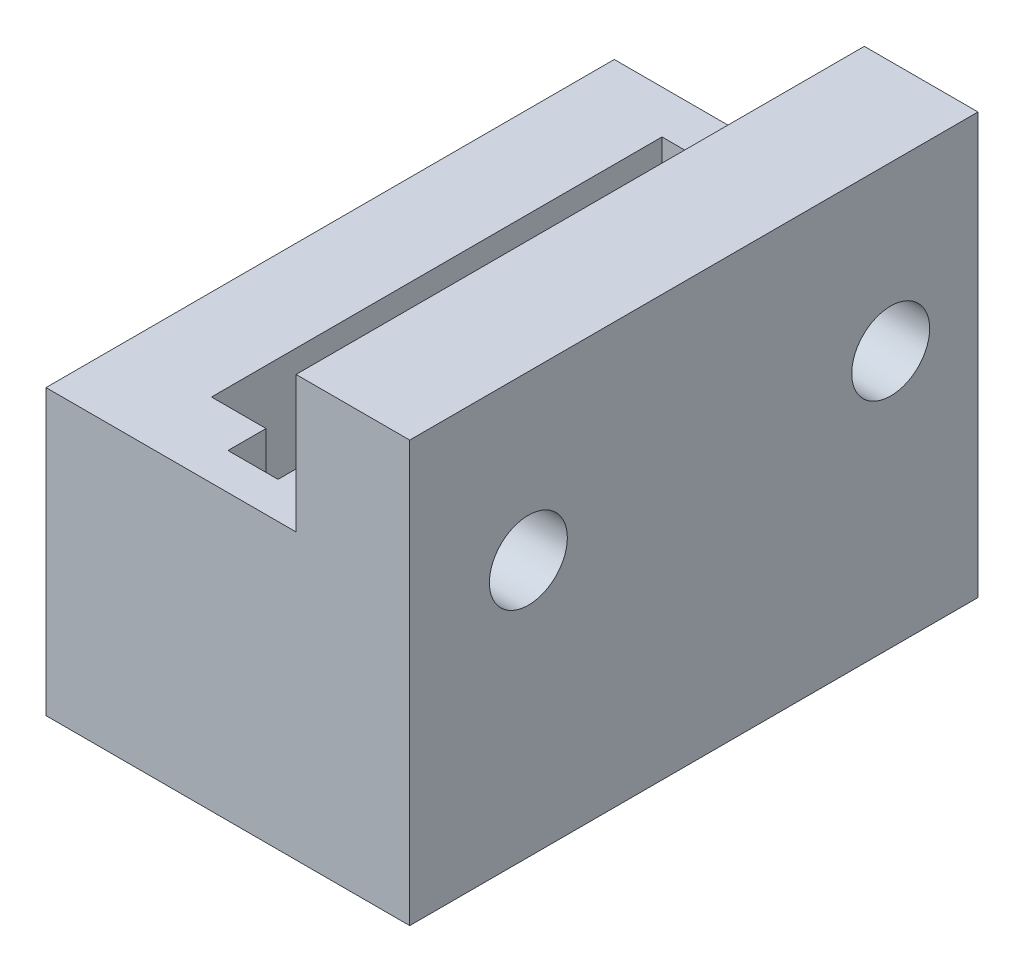
SolidWorks part; units mm, degrees
ref_plane "Front Plane" through (0, 0, 0) normal (0, 0, 1) x (1, 0, 0)
ref_plane "Top Plane" through (0, 0, 0) normal (0, 1, 0) x (1, 0, 0)
ref_plane "Right Plane" through (0, 0, 0) normal (1, 0, 0) x (0, 0, -1)
sketch "Sketch1" plane through (0, 0, 0) normal (0, 1, 0) x (1, 0, 0)
  line L1 (0, 0) -> (16, 0)
  line L2 (0, 0) -> (0, 25)
  line L3 (0, 25) -> (16, 25)
  line L4 (16, 0) -> (16, 25)
  dimension "D1" = 25
  dimension "D2" = 16
extrude "Boss-Extrude1" add sketch "Sketch1" along normal blind 12.5
sketch "Sketch2" plane through (0, 12.5, 0) normal (0, 1, 0) x (1, 0, 0)
  line L0 (16, 0) -> (16, 25) construction
  line L1 (4, 23.0983) -> (6.4, 23.0983)
  line L2 (4, 23.0983) -> (4, 3.2803)
  line L3 (4, 3.2803) -> (6.4, 3.2803)
  line L4 (11, 23.0983) -> (11, 3.2803)
  line L5 (7.5, 25) -> (7.5, 1.6053) construction
  line L6 (6.4, 23.0983) -> (6.4, 25)
  line L7 (16, 25) -> (0, 25) construction
  line L8 (6.4, 25) -> (8.6, 25)
  line L9 (8.6, 25) -> (8.6, 23.0983)
  line L10 (8.6, 23.0983) -> (11, 23.0983)
  line L11 (6.4, 3.2803) -> (6.4, 1.6053)
  line L12 (6.4, 1.6053) -> (8.6, 1.6053)
  line L13 (8.6, 1.6053) -> (8.6, 3.2803)
  line L14 (8.6, 3.2803) -> (11, 3.2803)
  point P13 (0, 0)
  dimension "D1" = 19.818
  dimension "D2" = 7
  dimension "D3" = 5
  dimension "D4" = 2.2
  dimension "D5" = 1.675
extrude "Cut-Extrude1" cut sketch "Sketch2" against normal blind 6.056
ref_plane "PLANE-CAVITY-MIDLINE" through (7.5, 0, 0) normal (1, 0, 0) x (0, 0, -1)
sketch "Sketch4" plane through (0, 12.5, 0) normal (0, 1, 0) x (1, 0, 0)
  line L0 (0, 0) -> (16, 0) construction
  line L1 (11, 0) -> (16, 0)
  line L2 (11, 0) -> (11, 25)
  line L3 (11, 25) -> (16, 25)
  line L4 (16, 0) -> (16, 25)
  line L5 (11, 3.2803) -> (11, 23.0983) construction
extrude "Boss-Extrude2" add sketch "Sketch4" along normal blind 6
sketch "Sketch3" plane through (16, 0, 0) normal (1, 0, 0) x (0, 0, -1)
  line L0 (0, 11.314) -> (25, 11.314) construction
  line L1 (0, 18.5) -> (0, 0) construction
  line L2 (25, 18.5) -> (25, 0) construction
  line L3 (5.2198, 11.314) -> (5.2198, 12.5) construction
  line L4 (0, 12.5) -> (25, 12.5) construction
  line L5 (15.8053, 11.314) -> (3.5053, 11.314) construction
  line L6 (5.2053, 10.144) -> (3.5053, 10.144) construction
  line L7 (5.2053, 12.544) -> (3.5053, 12.544) construction
  line L8 (21.1588, 12.5) -> (21.1588, 11.314) construction
  line L9 (5.2053, 10.144) -> (3.5053, 10.144) construction
  line L10 (5.2053, 12.544) -> (3.5053, 12.544) construction
  line L11 (3.5053, 12.544) -> (3.5053, 10.144) construction
  line L12 (13.1893, 6.444) -> (13.1893, 12.5) construction
  line L13 (3.2803, 6.444) -> (23.0983, 6.444) construction
  line L14 (23.0983, 12.5) -> (3.2803, 12.5) construction
  line L15 (23.0983, 6.444) -> (23.0983, 12.5) construction
  line L16 (3.2803, 6.444) -> (3.2803, 12.5) construction
  circle A0 centre (5.2198, 11.314) radius 1.7145
  circle A1 centre (21.1588, 11.314) radius 1.7145
  dimension "D1" = 3.429
  dimension "D2" = 14.2245
extrude "Cut-Extrude2" cut sketch "Sketch3" against normal up to surface (5 mm away) up to face at (11, 12.486, -12.8446)
sketch "Sketch6" plane through (0, 6.444, 0) normal (0, 1, 0) x (1, 0, 0)
  line L0 (5.875, 9.6053) -> (5.875, 3.2803) construction
  line L1 (4, 3.2803) -> (6.4, 3.2803) construction
  line L2 (9.125, 3.2803) -> (9.125, 9.6053) construction
  line L3 (8.6, 3.2803) -> (11, 3.2803) construction
  line L4 (9.125, 9.6053) -> (9.125, 17.6053) construction
  line L5 (9.125, 17.6053) -> (5.875, 17.6053) construction
  line L6 (5.875, 17.6053) -> (5.875, 9.6053) construction
  line L7 (5.875, 9.6053) -> (7.5, 9.6053) construction
  line L8 (7.5, -6.6308) -> (7.5, 6.6308) construction
  line L9 (7.5, 9.6053) -> (9.125, 9.6053) construction
  circle A0 centre (5.875, 9.6053) radius 0.5
  circle A1 centre (9.125, 9.6053) radius 0.5
  circle A2 centre (5.875, 17.6053) radius 0.5
  circle A3 centre (9.125, 17.6053) radius 0.5
  dimension "D1" = 1
  dimension "D2" = 8
  dimension "D3" = 1.625
  dimension "D4" = 6.325
extrude "Cut-Extrude3" cut sketch "Sketch6" against normal blind 4
sketch "Sketch7" plane through (0, 6.444, 0) normal (0, 1, 0) x (1, 0, 0)
  line L0 (7.5, 1.6053) -> (7.5, 5.6053) construction
  line L1 (6.4, 1.6053) -> (8.6, 1.6053) construction
  line L2 (7.5, -6.6308) -> (7.5, 6.6308) construction
  line L3 (7.5, 5.6053) -> (7.5, 13.6053) construction
  line L4 (7.5, 13.6053) -> (7.5, 21.6053) construction
  line L5 (8.6, 3.2803) -> (11, 3.2803) construction
  circle A0 centre (7.5, 21.6053) radius 1.5
  circle A1 centre (7.5, 13.6053) radius 1.5
  circle A2 centre (7.5, 5.6053) radius 1.5
  dimension "D2" = 8
  dimension "D3" = 8
  dimension "D1" = 2.325
  dimension "D4" = 3
extrude "Cut-Extrude4" cut sketch "Sketch7" against normal blind 2
